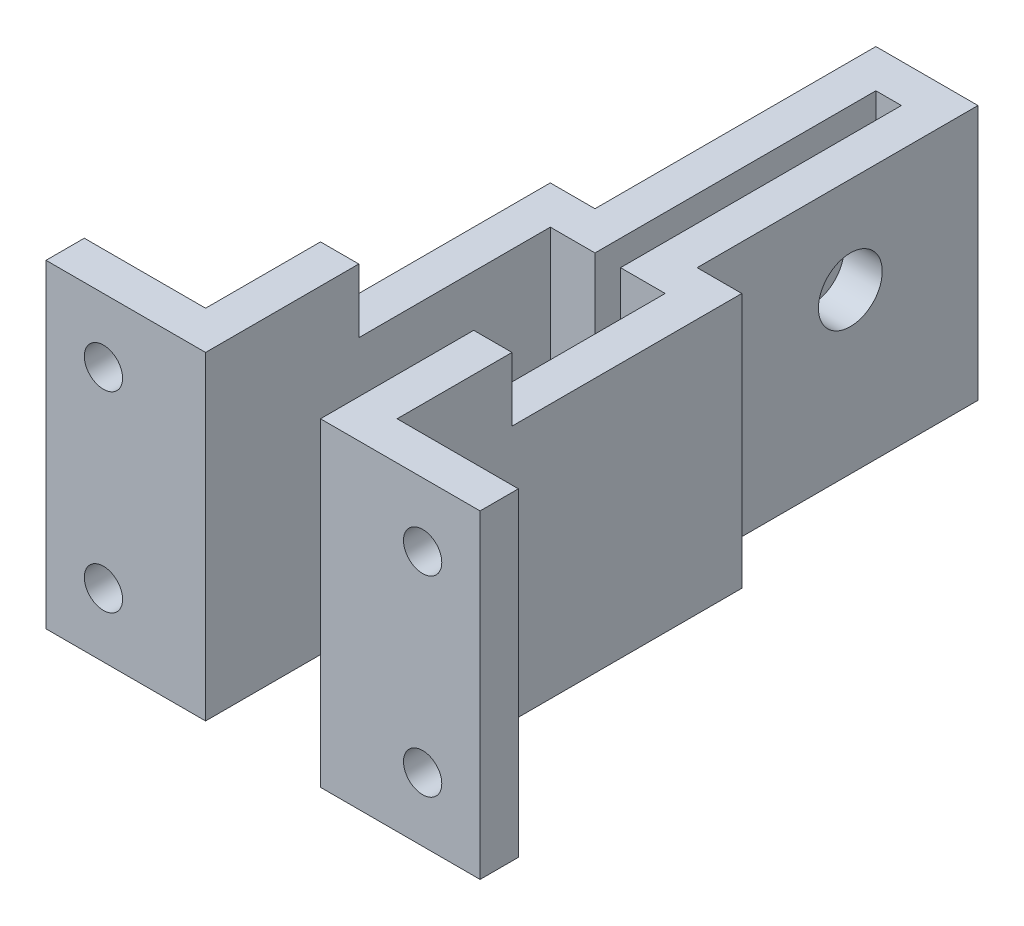
SolidWorks part; units mm, degrees
material "6061 Alloy"
ref_plane "Front Plane" through (0, 0, 0) normal (0, 0, 1) x (1, 0, 0)
ref_plane "Top Plane" through (0, 0, 0) normal (0, 1, 0) x (1, 0, 0)
ref_plane "Right Plane" through (0, 0, 0) normal (1, 0, 0) x (0, 0, -1)
sketch "Sketch9" plane through (0, 0, 0) normal (0, 1, 0) x (1, 0, 0)
  line L0 (-17, 0) -> (-4.5, 0)
  line L1 (-55, 0) -> (55, 0) construction
  line L2 (-4.5, 0) -> (-4.5, 27)
  line L3 (-4.5, 27) -> (-1, 27)
  line L4 (4.5, 27) -> (4.5, 0)
  line L5 (4.5, 0) -> (17, 0)
  line L6 (17, 0) -> (17, 3)
  line L7 (17, 3) -> (7.5, 3)
  line L8 (7.5, 3) -> (7.5, 30)
  line L9 (-1, 27) -> (-1, 49)
  line L10 (-7.5, 30) -> (-7.5, 3)
  line L11 (-7.5, 3) -> (-17, 3)
  line L12 (7.5, 30) -> (4, 30)
  line L13 (-17, 3) -> (-17, 0)
  line L14 (0, -55) -> (0, 55) construction
  line L15 (1, 49) -> (1, 27)
  line L16 (1, 27) -> (4.5, 27)
  line L17 (4, 30) -> (4, 52)
  line L18 (4, 52) -> (-4, 52)
  line L19 (-4, 52) -> (-4, 30)
  line L20 (-4, 30) -> (-7.5, 30)
  line L21 (-1, 49) -> (1, 49)
  dimension "D1" = 3
  dimension "D2" = 3
  dimension "D3" = 1
  dimension "D4" = 3
  dimension "D5" = 3
  dimension "D6" = 12.5
  dimension "D7" = 17
  dimension "D8" = 12.5
  dimension "D9" = 1
  dimension "D10" = 3
  dimension "D11" = 17
  dimension "D12" = 3
  dimension "D13" = 8
  dimension "D14" = 3
  dimension "D15" = 30
  dimension "D16" = 25
extrude "Boss-Extrude1" add sketch "Sketch9" along normal mid plane 25
sketch "Sketch11" plane through (0, 0, 0) normal (0, 0, 1) x (1, 0, 0)
  line L1 (-12.5, 7.5) -> (12.5, 7.5) construction
  line L2 (-12.5, 7.5) -> (-12.5, -7.5) construction
  line L3 (-12.5, -7.5) -> (12.5, -7.5) construction
  line L4 (12.5, 7.5) -> (12.5, -7.5) construction
  line L5 (-12.5, 7.5) -> (12.5, -7.5) construction
  line L6 (-12.5, -7.5) -> (12.5, 7.5) construction
  circle A0 centre (-12.5, 7.5) radius 1.5
  circle A1 centre (12.5, 7.5) radius 1.5
  circle A2 centre (12.5, -7.5) radius 1.5
  circle A3 centre (-12.5, -7.5) radius 1.5
  point P0 (0, 0)
  dimension "D1" = 3
  dimension "D2" = 25
  dimension "D3" = 15
extrude "Cut-Extrude6" cut sketch "Sketch11" against normal blind 30
sketch "Sketch12" plane through (0, 0, 0) normal (1, 0, 0) x (0, 0, -1)
  line L1 (52, 12.5) -> (12, 12.5)
  line L2 (52, 12.5) -> (52, 7.5)
  line L3 (52, 7.5) -> (12, 7.5)
  line L4 (12, 12.5) -> (12, 7.5)
  dimension "D1" = 5
  dimension "D2" = 40
extrude "Cut-Extrude7" cut sketch "Sketch12" against normal mid plane 30 contours L1 L4 L3 L2
sketch "Sketch13" plane through (0, 0, 0) normal (1, 0, 0) x (0, 0, -1)
  line L0 (18.7, 0) -> (-18.7, 0) construction
  line L2 (52, 7.5) -> (52, -12.5) construction
  circle A0 centre (42, 0) radius 2.5
  dimension "D1" = 5
  dimension "D2" = 10
extrude "Cut-Extrude8" cut sketch "Sketch13" against normal mid plane 50
